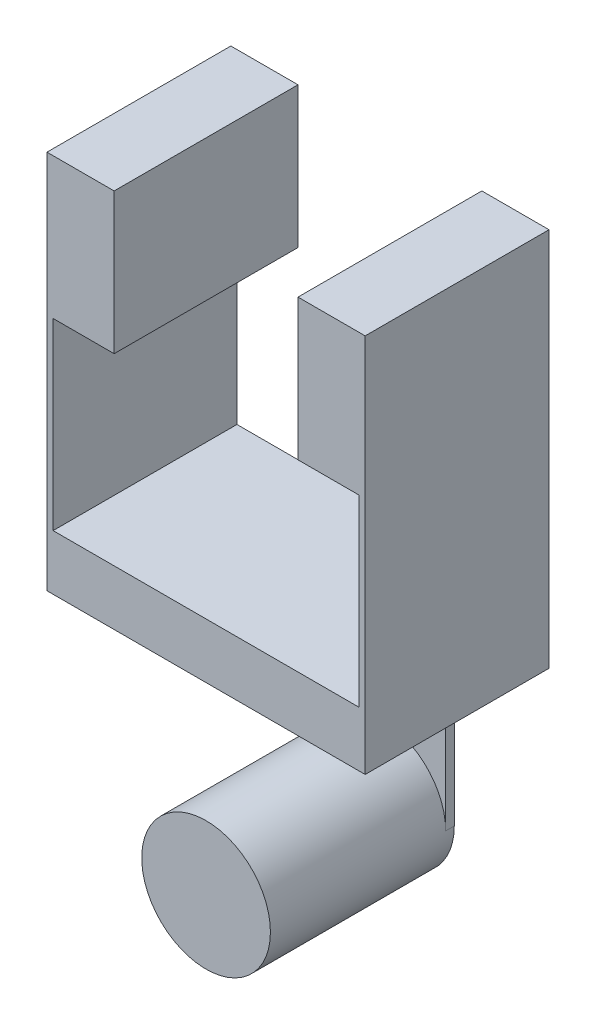
SolidWorks part; units mm, degrees
ref_plane "Front Plane" through (0, 0, 0) normal (0, 0, 1) x (1, 0, 0)
ref_plane "Top Plane" through (0, 0, 0) normal (0, 1, 0) x (1, 0, 0)
ref_plane "Right Plane" through (0, 0, 0) normal (1, 0, 0) x (0, 0, -1)
sketch "Sketch1" plane through (0, 0, 0) normal (0, 0, 1) x (1, 0, 0)
  circle A0 centre (0, 0) radius 13.335
  dimension "D1" = 26.67
extrude "FeatureA" add sketch "Sketch1" against normal blind 38.1 contours A0
ref_plane "Plane1" through (0, 0, -38.1) normal (0, 0, -1) x (-1, 0, 0)
sketch "Sketch2" plane through (0, 0, -38.1) normal (0, 0, -1) x (-1, 0, 0)
  line L0 (-13.335, 0) -> (13.335, 0)
  line L1 (13.335, 0) -> (13.335, 38.1)
  line L2 (13.335, 38.1) -> (-13.335, 38.1)
  line L3 (-13.335, 38.1) -> (-13.335, 0)
  circle A0 centre (0, 0) radius 13.335 construction
  dimension "D1" = 38.1
extrude "FeatureB" add sketch "Sketch2" against normal blind 1.778 contours L2 L3 L0 L1
ref_plane "Plane2" through (0, 38.1, 0) normal (0, 1, 0) x (1, 0, 0)
sketch "Sketch3" plane through (0, 38.1, 0) normal (0, 1, 0) x (1, 0, 0)
  line L0 (0, 38.1) -> (-32.9692, 38.1)
  line L1 (14.6685, 38.1) -> (-14.6685, 38.1) construction
  line L2 (-32.9692, 38.1) -> (-32.9692, 0)
  line L3 (-32.9692, 0) -> (32.9692, 0)
  line L4 (32.9692, 0) -> (32.9692, 38.1)
  line L5 (32.9692, 38.1) -> (0, 38.1)
  line L6 (32.9692, 19.05) -> (-32.9692, 19.05) construction
  line L9 (0, 38.1) -> (0, 0) construction
  dimension "D1" = 65.9384
  dimension "D2" = 38.1
extrude "FeatureC" add sketch "Sketch3" along normal blind 11.43
sketch "Sketch4" plane through (0, 49.53, 0) normal (0, 1, 0) x (1, 0, 0)
  line L0 (34.5757, 38.1) -> (-34.5757, 38.1) construction
  line L1 (32.9692, 0) -> (31.6992, 0)
  line L2 (32.9692, 0) -> (32.9692, 38.1)
  line L3 (32.9692, 38.1) -> (31.6992, 38.1)
  line L4 (31.6992, 0) -> (31.6992, 38.1)
  line L5 (0, 38.1) -> (0, 0) construction
  line L6 (32.9692, 38.1) -> (-32.9692, 38.1) construction
  line L7 (-32.9692, 0) -> (32.9692, 0) construction
  line L8 (-32.9692, 38.1) -> (-31.6992, 38.1)
  line L9 (-31.6992, 0) -> (-31.6992, 38.1)
  line L10 (-32.9692, 0) -> (-31.6992, 0)
  line L11 (-32.9692, 0) -> (-32.9692, 38.1)
  dimension "D1" = 1.27
extrude "FeatureD" add sketch "Sketch4" along normal blind 38.0746
sketch "Sketch7" plane through (0, 87.6046, 0) normal (0, 1, 0) x (1, 0, 0)
  line L0 (36.2661, 38.1) -> (-36.2661, 38.1) construction
  line L1 (32.9692, 0) -> (19.05, 0)
  line L2 (32.9692, 0) -> (32.9692, 38.1)
  line L3 (32.9692, 38.1) -> (19.05, 38.1)
  line L4 (19.05, 0) -> (19.05, 38.1)
  line L5 (31.6992, 38.1) -> (31.6992, 0) construction
  line L6 (0, 0) -> (0, 41.6455) construction
  line L7 (-32.9692, 38.1) -> (-19.05, 38.1)
  line L8 (-19.05, 0) -> (-19.05, 38.1)
  line L9 (-32.9692, 0) -> (-19.05, 0)
  line L10 (-32.9692, 0) -> (-32.9692, 38.1)
  dimension "D1" = 12.6492
extrude "Boss-Extrude5" add sketch "Sketch7" along normal blind 29.21
ref_plane "Plane3" through (0, 87.63, 0) normal (0, 1, 0) x (1, 0, 0)
equation "\"La\"= 1.5"
equation "\"Da\"= 1.05"
equation "\"Wb\"= \"La\""
equation "\"Lb\"= \"La\""
equation "\"tb\"= 0.07"
equation "\"bc\"= 0.498 + 0.9992 * 2"
equation "\"Lc\"= \"La\""
equation "\"hc\"= 0.45"
equation "\"hd\"= 1.499"
equation "\"Ld\"= \"La\""
equation "\"td\"= \"F\" / ( \"hd\" * \"stress\" ) + .002"
equation "\"be\"= 0.498"
equation "\"Le\"= \"La\""
equation "\"he\"= 1.15"
equation "\"E\"= 29 * 10 ^ 6"
equation "\"Sy\"= 36000"
equation "\"deflection\"= 0.005"
equation "\"F\"= 650"
equation "\"stress\"= 9000"
